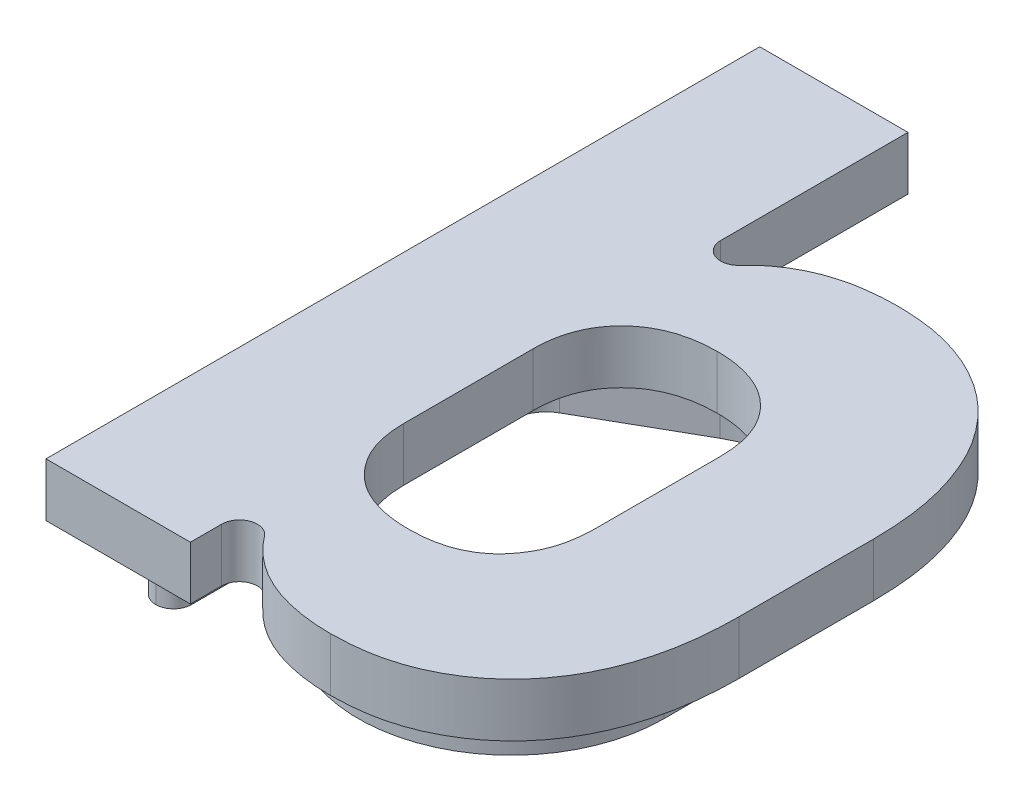
SolidWorks part; units mm, degrees
material "Сосна"
ref_plane "Спереди" through (0, 0, 0) normal (0, 0, 1) x (1, 0, 0)
ref_plane "Сверху" through (0, 0, 0) normal (0, 1, 0) x (1, 0, 0)
ref_plane "Справа" through (0, 0, 0) normal (1, 0, 0) x (0, 0, -1)
sketch "Эскиз b" plane through (0, 0, 0) normal (0, 1, 0) x (1, 0, 0)
  line L0 (0, 200) -> (41.5444, 200)
  line L1 (41.5444, 200) -> (41.5444, 147.5019)
  line L3 (135.4146, 96.4343) -> (135.4146, 58.8141)
  line L5 (40.4626, 8.7551) -> (40.4626, 0)
  line L6 (40.4626, 0) -> (0, 0)
  line L7 (0, 0) -> (0, 200)
  line L8 (93.9081, 60.016) -> (93.9081, 94.9519)
  line L9 (41.5444, 94.9519) -> (41.5444, 58.6138)
  line L10 (0, -24.9193) -> (0, 221.7067) construction
  line L11 (-26.4652, 0) -> (175.2563, 0) construction
  arc A0 (41.5444, 147.5019) -> (50.2847, 144.1838) centre (46.5444, 147.5019) ccw
  arc A1 (49.4869, 11.7225) -> (40.4626, 8.7551) centre (45.4626, 8.7551) ccw
  spline S2 degree 3 poles (50.2847, 144.1838) (50.4667, 144.3889) (51.3395, 145.3456) (53.0349, 146.9784) (55.5142, 148.9211) (58.1964, 150.6994) (61.1082, 152.21) (64.1748, 153.5515) (67.4504, 154.5623) (70.8771, 155.4462) (75.8304, 156.1473) (79.6485, 156.4337) (82.2495, 156.4103) knots 0.335543 0.335543 0.335543 0.335543 0.351035 0.408678 0.468317 0.52881 0.590251 0.653473 0.717675 0.783752 0.853236 1 1 1 1
  spline S3 degree 3 poles (82.2495, 156.4103) (86.12, 156.3503) (91.8434, 155.977) (99.1079, 154.1477) (104.1309, 152.3066) (108.8363, 149.9663) (113.2249, 147.202) (117.2699, 143.9634) (120.9612, 140.2655) (124.287, 136.1265) (127.2421, 131.5758) (129.7088, 126.5729) (131.795, 121.1992) (133.4356, 115.4608) (135.0073, 107.2042) (135.3941, 100.786) (135.4146, 96.4343) knots 0 0 0 0 0.128788 0.189121 0.248183 0.306088 0.363292 0.420078 0.477771 0.536427 0.59608 0.657554 0.72129 0.787255 0.855435 1 1 1 1
  spline S4 degree 3 poles (135.4146, 58.8141) (135.3883, 54.3034) (135.0181, 47.671) (133.4382, 39.1609) (131.8091, 33.3112) (129.7089, 27.8746) (127.2328, 22.8249) (124.2869, 18.2042) (120.9761, 13.9837) (117.2576, 10.2469) (113.2301, 6.924) (108.838, 4.0847) (104.1433, 1.6529) (99.1087, -0.2189) (91.8501, -2.1047) (86.1235, -2.5283) (82.2495, -2.5641) knots 0 0 0 0 0.147997 0.217046 0.28345 0.346798 0.407897 0.467542 0.52615 0.583432 0.64006 0.697021 0.754598 0.813074 0.872761 1 1 1 1
  spline S5 degree 3 poles (82.2495, -2.5641) (79.649, -2.5917) (75.818, -2.3128) (70.8805, -1.465) (67.4407, -0.5695) (64.173, 0.5415) (61.0957, 1.9519) (58.1806, 3.5879) (55.5118, 5.5316) (53.017, 7.6325) (51.0319, 9.7311) (49.9177, 11.1382) (49.4869, 11.7225) knots 0 0 0 0 0.141704 0.208996 0.272941 0.335358 0.396958 0.457301 0.517326 0.57673 0.634944 0.674514 0.674514 0.674514 0.674514
  spline S6 degree 3 poles (41.5444, 58.6138) (41.5695, 55.2564) (42.2708, 50.2259) (45.3176, 44.3512) (48.358, 40.5764) (52.2159, 37.4627) (58.6568, 34.4686) (64.1233, 33.7033) (67.8665, 33.734) knots 0 0 0 0 0.24798 0.363834 0.482443 0.601818 0.724705 1 1 1 1
  spline S7 degree 3 poles (67.8665, 33.734) (71.5967, 33.7231) (77.1104, 34.4147) (83.4487, 37.6377) (87.2412, 40.8681) (90.2035, 44.8488) (93.2535, 51.0903) (93.852, 56.4481) (93.9081, 60.016) knots 0 0 0 0 0.268987 0.38851 0.505395 0.623022 0.742123 1 1 1 1
  spline S8 degree 3 poles (93.9081, 94.9519) (93.8959, 98.4923) (93.228, 103.7674) (90.0615, 109.8203) (86.913, 113.5199) (83.0602, 116.506) (76.7854, 119.4201) (71.4862, 120.1613) (67.8665, 120.1122) knots 0 0 0 0 0.261299 0.379584 0.496338 0.615056 0.734226 1 1 1 1
  spline S9 degree 3 poles (67.8665, 120.1122) (64.2376, 120.1027) (58.892, 119.3824) (52.5583, 116.4352) (48.6496, 113.3844) (45.4435, 109.656) (42.317, 103.6157) (41.5035, 98.4483) (41.5444, 94.9519) knots 0 0 0 0 0.266055 0.387077 0.506835 0.626018 0.743974 1 1 1 1
  dimension "D3" = 10
  dimension "D4" = 10
  dimension "D1" = 40.4626
  dimension "D2" = 41.5444
extrude "b" add sketch "Эскиз b" along normal blind 15
sketch "Эскиз крепежа подсветки" plane through (0, 0, 0) normal (0, 1, 0) x (1, 0, 0)
  line L0 (20.77, 10) -> (20.77, 190)
  line L1 (34.8054, 34.0497) -> (57.9406, 20.729)
  line L2 (114.665, 53.5235) -> (114.665, 100.2754)
  line L3 (57.012, 133.7786) -> (20.77, 113.1261)
  arc A0 (57.9406, 20.729) -> (114.665, 53.5235) centre (76.8229, 53.5235) ccw
  arc A1 (114.665, 100.2754) -> (57.012, 133.7786) centre (76.1038, 100.2754) ccw
  dimension "D1" = 114.665
  dimension "D2" = 20.77
  dimension "D3" = 10
  dimension "D4" = 190
extrude "Крепёж подсветки" add sketch "Эскиз крепежа подсветки" against normal blind 15 thin thin type mid plane wall 10
fillet "Внешнее скруглнеие под ленту" radius 5 6 edges at (37.3003, -7.5, -38.3828) (32.3105, -7.5, -29.7166) (25.77, -7.5, -10) (15.77, -7.5, -10) (15.77, -7.5, -190) (25.77, -7.5, -190)
fillet "Внутреннее скругление под ленту" radius 10 2 edges at (25.77, -7.5, -110.2205) (25.77, -7.5, -121.7302)
sketch "Эскиз разметки под шурупы" plane through (0, 0, 0) normal (0, 1, 0) x (1, 0, 0)
  circle A0 centre (20.77, 185) radius 1.5
  circle A1 centre (20.77, 15) radius 1.5
  circle A2 centre (114.665, 75) radius 1.5
  point P6 (0, 0)
  dimension "D1" = 3
  dimension "D2" = 3
  dimension "D3" = 3
  dimension "D4" = 20.77
  dimension "D6" = 15
  dimension "D8" = 93.895
  dimension "D9" = 60
  dimension "D5" = 170
extrude "Разметка под шурупы" cut sketch "Эскиз разметки под шурупы" against normal through all
equation "\"drill\"= 3мм"
equation "\"D1@Эскиз разметки под шурупы\" = \"drill\""
equation "\"D2@Эскиз разметки под шурупы\" = \"drill\""
equation "\"D3@Эскиз разметки под шурупы\" = \"drill\""
